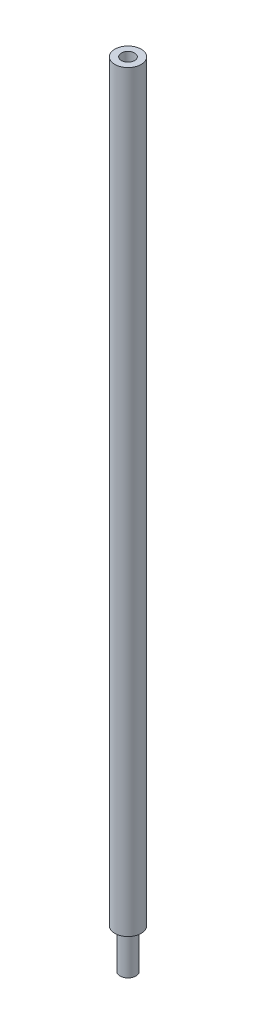
SolidWorks part; units mm, degrees
ref_plane "Front Plane" through (0, 0, 0) normal (0, 0, 1) x (1, 0, 0)
ref_plane "Top Plane" through (0, 0, 0) normal (0, 1, 0) x (1, 0, 0)
ref_plane "Right Plane" through (0, 0, 0) normal (1, 0, 0) x (0, 0, -1)
sketch "Sketch1" plane through (0, 0, 0) normal (1, 0, 0) x (0, 0, -1)
  line L0 (0, 68.844) -> (0, -249.3934) construction
  line L1 (0, 64.1903) -> (5, 64.1903)
  line L2 (5, 61.1903) -> (5, -220.8097)
  line L3 (5, 64.1903) -> (5, 61.1903)
  line L5 (5, -220.8097) -> (3, -220.8097)
  line L6 (3, -220.8097) -> (3, -235.8097)
  line L7 (3, -235.8097) -> (0, -235.8097)
  line L8 (0, 64.1903) -> (0, -235.8097)
  dimension "D2" = 5
  dimension "D5" = 2
  dimension "D6" = 15
revolve "Revolve1" add sketch "Sketch1" angle 360 about L0
shell "Shell1" thickness 1 rebuild error yes
sketch "Sketch2" plane through (0, -234.8097, 0) normal (0, 1, 0) x (1, 0, 0)
  circle A0 centre (0, 0) radius 2 construction
  circle A1 centre (0, 0) radius 2
extrude "Cut-Extrude1" cut sketch "Sketch2" against normal through all
sketch "Sketch3" plane through (0, 64.1903, 0) normal (0, 1, 0) x (1, 0, 0)
  circle A0 centre (0, 0) radius 2.5
  dimension "D1" = 5
sketch "Sketch4" plane through (0, 64.1903, 0) normal (0, 1, 0) x (1, 0, 0)
  circle A0 centre (0, 0) radius 5 construction
  circle A1 centre (0, 0) radius 5
extrude "Boss-Extrude1" add sketch "Sketch4" against normal blind 15
extrude "Cut-Extrude2" cut sketch "Sketch3" against normal blind 15 contours A0
shell "Shell2" thickness 1 removed face at (0, 49.1903, 2.5)
sketch "Sketch5" plane through (0, -234.8097, 0) normal (0, -1, 0) x (1, 0, 0)
  circle A0 centre (0, 0) radius 2 construction
  circle A1 centre (0, 0) radius 2
extrude "Cut-Extrude3" cut sketch "Sketch5" against normal blind 5
